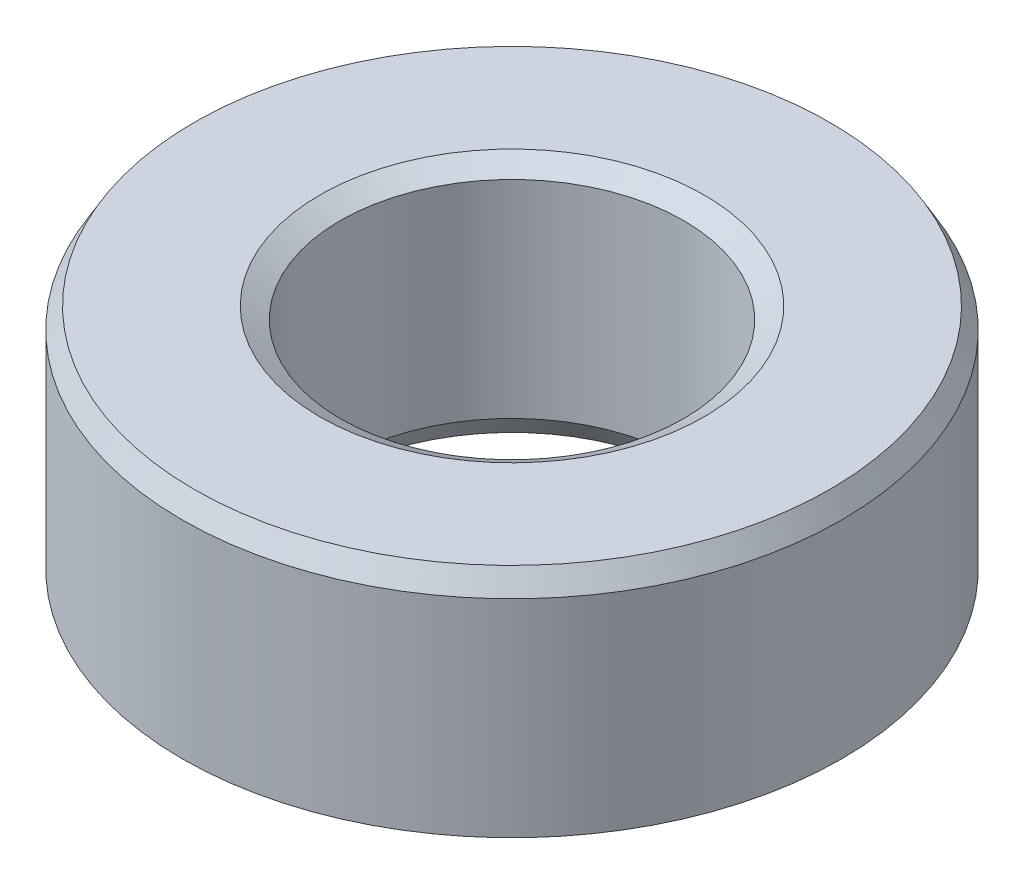
SolidWorks part; units mm, degrees
ref_plane "Front Plane" through (0, 0, 0) normal (0, 0, 1) x (1, 0, 0)
ref_plane "Top Plane" through (0, 0, 0) normal (0, 1, 0) x (1, 0, 0)
ref_plane "Right Plane" through (0, 0, 0) normal (1, 0, 0) x (0, 0, -1)
sketch "Sketch1" plane through (0, 0, 0) normal (0, 1, 0) x (1, 0, 0)
  circle A0 centre (0, 0) radius 15
  dimension "SLEEVE_OD" = 30
extrude "Boss-Extrude1" add sketch "Sketch1" along normal blind 10.8877
sketch "Sketch2" plane through (0, 0, 0) normal (0, 1, 0) x (1, 0, 0)
  circle A0 centre (0, 0) radius 7.8086
  dimension "BORE_D" = 15.6172
extrude "Cut-Extrude1" cut sketch "Sketch2" along normal through all
chamfer "Chamfer1" distance 0.9344 angle 30 4 edges at (0, 10.8877, 7.8086) (0, 0, 7.8086) (0, 0, 15) (0, 10.8877, 15) first distance on face at (0, 10.8877, 7.8086) first distance on face at (0, 0, 7.8086) first distance on face at (0, 10.8877, 15)
